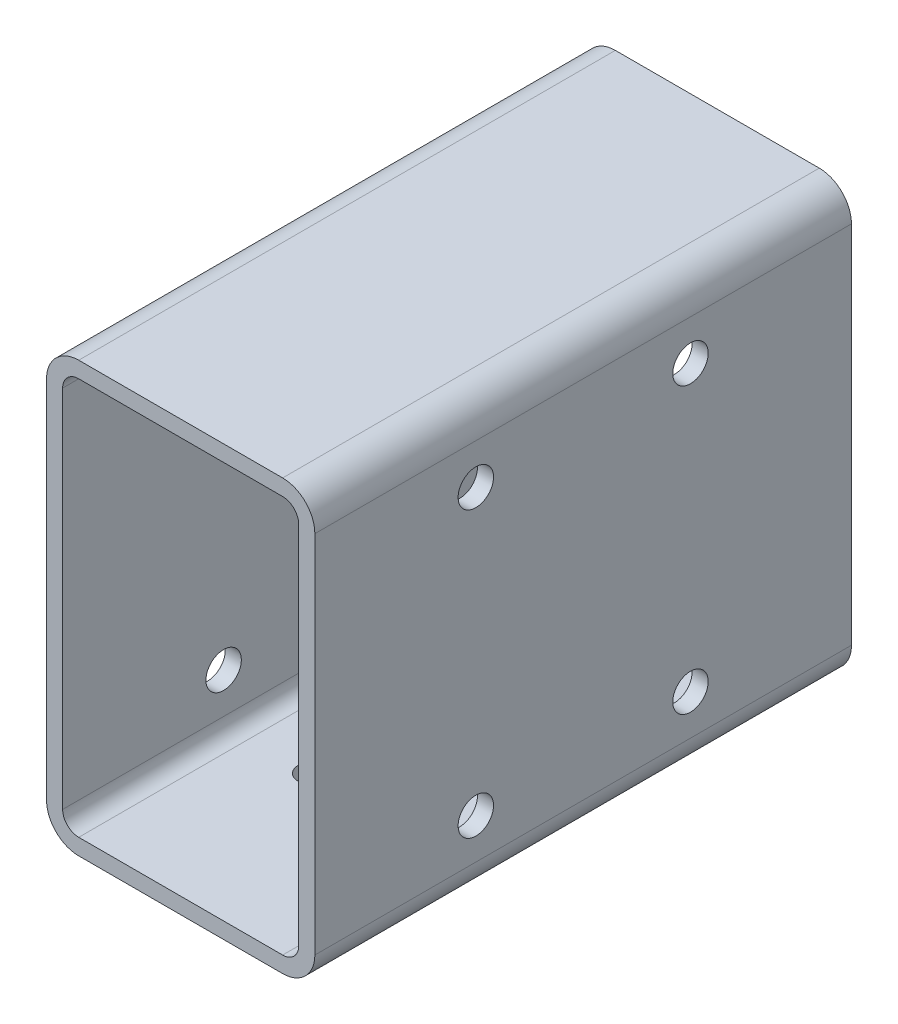
SolidWorks part; units mm, degrees
ref_plane "Front Plane" through (0, 0, 0) normal (0, 0, 1) x (1, 0, 0)
ref_plane "Top Plane" through (0, 0, 0) normal (0, 1, 0) x (1, 0, 0)
ref_plane "Right Plane" through (0, 0, 0) normal (1, 0, 0) x (0, 0, -1)
sketch "Sketch1" plane through (0, 0, 0) normal (0, 0, 1) x (1, 0, 0)
  line L0 (19, 40) -> (-19, 40)
  line L1 (19, -37) -> (-19, -37)
  line L2 (22, -34) -> (22, 34)
  line L3 (19, 37) -> (-19, 37)
  line L4 (-22, -34) -> (-22, 34)
  line L5 (22, -37) -> (-22, 37) construction
  line L6 (22, 37) -> (-22, -37) construction
  line L7 (-25, -34) -> (-25, 34)
  line L8 (19, -40) -> (-19, -40)
  line L9 (25, -34) -> (25, 34)
  line L10 (22, -37) -> (-22, -37) construction
  line L11 (22, -37) -> (22, 37) construction
  line L12 (-22, -37) -> (-22, 37) construction
  line L13 (22, 37) -> (-22, 37) construction
  line L14 (-25, -40) -> (-25, 40) construction
  line L15 (25, -40) -> (-25, -40) construction
  line L16 (25, -40) -> (25, 40) construction
  line L17 (25, 40) -> (-25, 40) construction
  arc A0 (19, -37) -> (22, -34) centre (19, -34) ccw
  arc A1 (-19, -37) -> (-22, -34) centre (-19, -34) cw
  arc A2 (-19, 37) -> (-22, 34) centre (-19, 34) ccw
  arc A3 (22, 34) -> (19, 37) centre (19, 34) ccw
  arc A4 (-25, -34) -> (-19, -40) centre (-19, -34) ccw
  arc A5 (19, -40) -> (25, -34) centre (19, -34) ccw
  arc A6 (19, 40) -> (25, 34) centre (19, 34) cw
  arc A7 (-19, 40) -> (-25, 34) centre (-19, 34) ccw
  point P0 (0, 0)
  dimension "D4" = 3
  dimension "D5" = 6
  dimension "D1" = 50
  dimension "D2" = 80
  dimension "D3" = 3
extrude "Boss-Extrude1" add sketch "Sketch1" along normal mid plane 100
sketch "Sketch2" plane through (-25, 0, 0) normal (-1, 0, 0) x (0, 0, 1)
  line L1 (20, -26.5) -> (-20, -26.5) construction
  line L2 (20, -26.5) -> (20, 26.5) construction
  line L3 (20, 26.5) -> (-20, 26.5) construction
  line L4 (-20, -26.5) -> (-20, 26.5) construction
  line L5 (20, -26.5) -> (-20, 26.5) construction
  line L6 (20, 26.5) -> (-20, -26.5) construction
  circle A0 centre (-20, 26.5) radius 3.3
  circle A1 centre (20, 26.5) radius 3.3
  circle A2 centre (20, -26.5) radius 3.3
  circle A3 centre (-20, -26.5) radius 3.3
  point P0 (0, 0)
  dimension "D3" = 6.6
  dimension "D1" = 40
  dimension "D2" = 53
extrude "Cut-Extrude1" cut sketch "Sketch2" against normal through all
sketch "Sketch3" plane through (0, -37, 0) normal (0, 1, 0) x (1, 0, 0)
  line L0 (0, 0) -> (3.6, 0) construction
  line L1 (25, -50) -> (25, 50) construction
  line L2 (14.85, 18) -> (-7.65, 18) construction
  line L3 (14.85, 18) -> (14.85, -18) construction
  line L4 (14.85, -18) -> (-7.65, -18) construction
  line L5 (-7.65, 18) -> (-7.65, -18) construction
  line L6 (14.85, 18) -> (-7.65, -18) construction
  line L7 (14.85, -18) -> (-7.65, 18) construction
  line L8 (-25, -50) -> (-25, 50) construction
  circle A0 centre (-7.65, 0) radius 2.5
  circle A1 centre (-7.65, 18) radius 2.5
  circle A2 centre (-7.65, -18) radius 2.5
  circle A3 centre (14.85, 18) radius 2.5
  circle A4 centre (14.85, -18) radius 2.5
  dimension "D1" = 5
  dimension "D2" = 36
  dimension "D4" = 10.15
  dimension "D3" = 17.35
extrude "Cut-Extrude2" cut sketch "Sketch3" against normal through all
equation "\"length\"= 100"
equation "\"D1@Boss-Extrude1\"=\"length\""
equation "\"M5_tap\"=4.2mm"
equation "\"M5_clearence\"=5.5mm"
equation "\"M6_tap\"=5mm"
equation "\"M6_clearence\"=6.6mm"
equation "\"D3@Sketch2\"=\"M6_clearence\""
equation "\"D1@Sketch3\"=\"M6_tap\""
